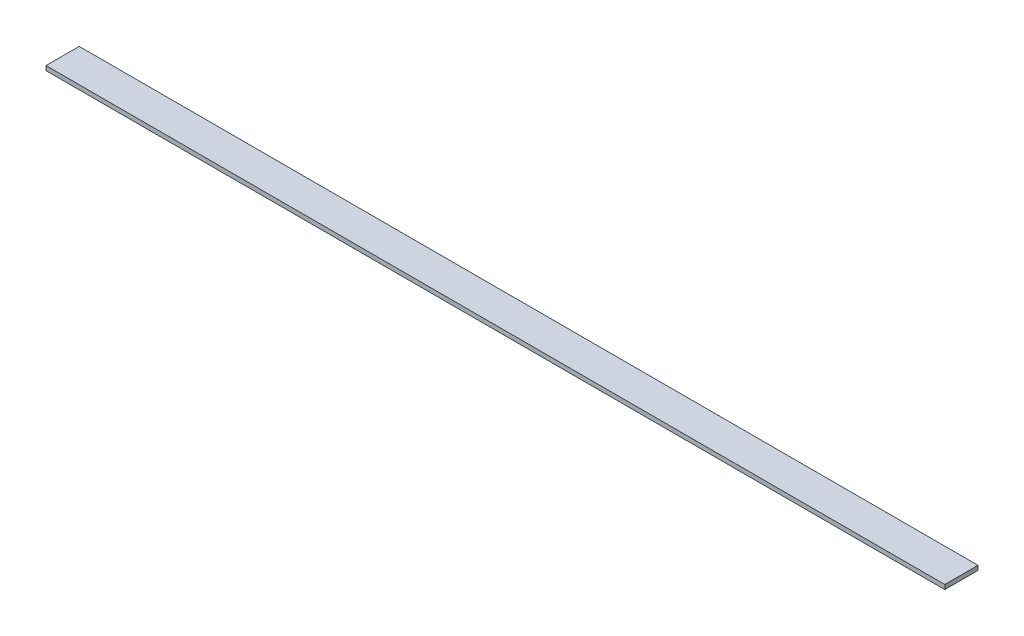
SolidWorks part; units mm, degrees
material "1060 Сплав"
ref_plane "Front" through (0, 0, 0) normal (0, 0, 1) x (1, 0, 0)
ref_plane "Top" through (0, 0, 0) normal (0, 1, 0) x (1, 0, 0)
ref_plane "Right" through (0, 0, 0) normal (1, 0, 0) x (0, 0, -1)
sketch "Эскиз1" plane through (0, 0, 0) normal (1, 0, 0) x (0, 0, -1)
  line L1 (0, 0) -> (15, 0)
  line L2 (0, 0) -> (0, 2)
  line L3 (0, 2) -> (15, 2)
  line L4 (15, 0) -> (15, 2)
  dimension "D1" = 2
  dimension "D2" = 15
base flange "Базовая кромка1" sketch "Эскиз1" thickness 406 reverse thickness direction no parameters "D1"=0.8
sketch "Сгиб-Линии1" [suppressed] plane through (0, 0, 0) normal (0, 1, 0) x (1, 0, 0)
sketch "Граничная рамка1" [suppressed] plane through (0, 0, 0) normal (0, 1, 0) x (1, 0, 0)
sheet metal parameters "Листовой металл1" thickness 406 parameters "D1"=0.8
flat pattern "Развертка1" [suppressed]
sketch "Сгиб-Линии2" plane through (0, 0, 0) normal (0, 1, 0) x (1, 0, 0)
sketch3d "Граничная рамка2" [suppressed]
  line L0 (15, 0, 0) -> (0, 0, 0) construction
  line L1 (15, 2, 0) -> (0, 2, 0) construction
  line L2 (15, 0, 0) -> (15, 2, 0) construction
  line L3 (0, 0, 0) -> (0, 2, 0) construction
